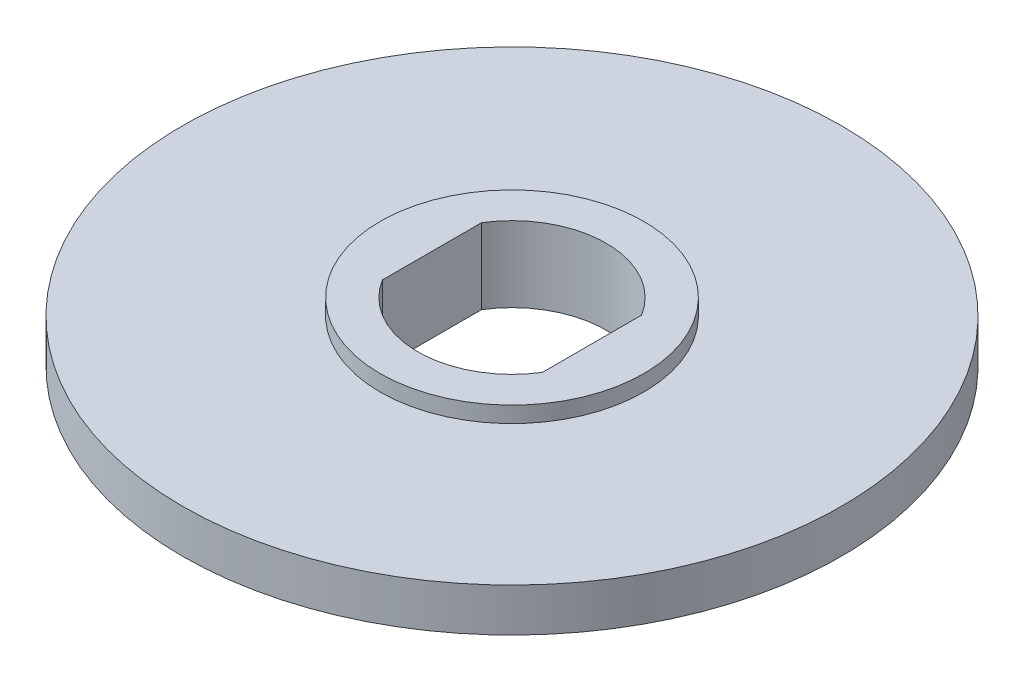
SolidWorks part; units mm, degrees
ref_plane "Front Plane" through (0, 0, 0) normal (0, 0, 1) x (1, 0, 0)
ref_plane "Top Plane" through (0, 0, 0) normal (0, 1, 0) x (1, 0, 0)
ref_plane "Right Plane" through (0, 0, 0) normal (1, 0, 0) x (0, 0, -1)
sketch "Sketch1" plane through (0, 0, 0) normal (0, 1, 0) x (1, 0, 0)
  line L1 (-4.25, 2.6339) -> (4.25, 2.6339)
  line L2 (-4.25, 2.6339) -> (-4.25, -2.6339)
  line L3 (-4.25, -2.6339) -> (4.25, -2.6339)
  line L4 (4.25, 2.6339) -> (4.25, -2.6339)
  line L5 (-4.25, 2.6339) -> (4.25, -2.6339) construction
  line L6 (-4.25, -2.6339) -> (4.25, 2.6339) construction
  circle A0 centre (0, 0) radius 5
  circle A1 centre (0, 0) radius 17.5
  circle A2 centre (0, 0) radius 7
  dimension "D1" = 10
  dimension "D2" = 35
  dimension "D3" = 8.5
  dimension "D4" = 2
extrude "Boss-Extrude1" add sketch "Sketch1" along normal mid plane 4 contours A2 A0 | L4 A0 | L2 A0 region at (-4.552, 0, 0) region at (4.552, 0, 0) region at (-6.802, 0, 0)
extrude "Boss-Extrude2" add sketch "Sketch1<3>" along normal mid plane 2.3 contours A1 A2 region at (-17.005, 0, 0)
sketch "Sketch1<3>" plane through (0, 0, 0) normal (0, 1, 0) x (1, 0, 0) same geometry as "Sketch1"
